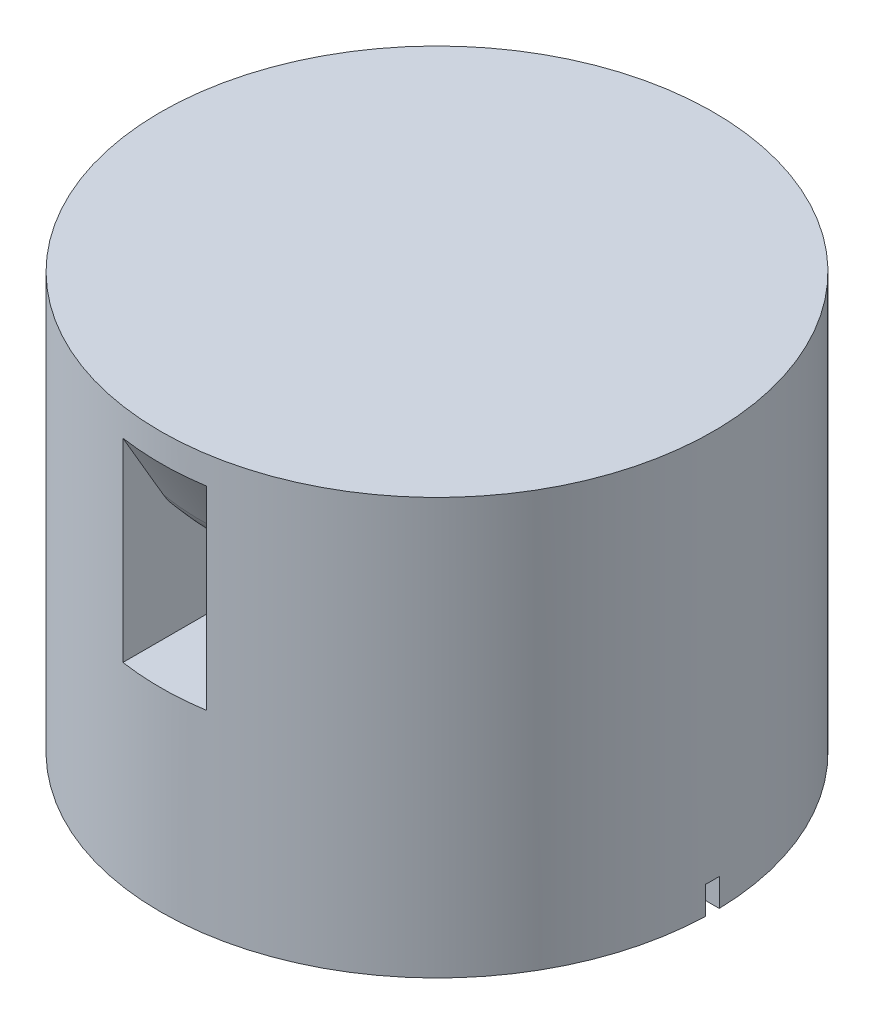
SolidWorks part; units mm, degrees
ref_plane "Front Plane" through (0, 0, 0) normal (0, 0, 1) x (1, 0, 0)
ref_plane "Top Plane" through (0, 0, 0) normal (0, 1, 0) x (1, 0, 0)
ref_plane "Right Plane" through (0, 0, 0) normal (1, 0, 0) x (0, 0, -1)
sketch "Sketch4" plane through (0, 0, 0) normal (0, 1, 0) x (1, 0, 0)
  circle A0 centre (-20.5796, -33.8554) radius 12.6543
extrude "Boss-Extrude3" add sketch "Sketch4" along normal blind 19.05
sketch "Sketch5" plane through (0, 19.05, 0) normal (0, 1, 0) x (1, 0, 0)
  line L0 (-10.0887, -40.9316) -> (-20.5796, -33.8554)
  line L1 (-20.5796, -33.8554) -> (-20.5796, -46.5097)
  circle A1 centre (-20.5796, -33.8554) radius 12.6543 construction
  dimension "D1" = 12.6543
  dimension "D2" = 12.6543
  dimension "D3" = 56
ref_plane "Plane6" through (0, 0, 46.5097) normal (0, 0, 1) x (1, 0, 0)
sketch "Sketch6" plane through (0, 0, 46.5097) normal (0, 0, 1) x (1, 0, 0)
  line L1 (-22.4389, 12.7) -> (-18.6289, 12.7)
  line L2 (-22.4389, 12.7) -> (-22.4389, 8.89)
  line L3 (-22.4389, 8.89) -> (-18.6289, 8.89)
  line L4 (-18.6289, 12.7) -> (-18.6289, 8.89)
  line L7 (-7.9253, 19.05) -> (-33.2339, 19.05) construction
  dimension "D1" = 3.81
  dimension "D4" = 6.35
sketch "Sketch8" plane through (0, 19.05, 0) normal (0, 1, 0) x (1, 0, 0)
  line L0 (-20.5796, -33.8554) -> (-33.2339, -33.8554)
  line L1 (-33.2339, -33.8554) -> (-7.9253, -33.8554)
  circle A0 centre (-20.5796, -33.8554) radius 12.6543 construction
extrude "Cut-Extrude5" cut sketch "Sketch6" against normal blind 5.08 contours L1 L4 L3 L2
chamfer "Chamfer4" distance 5.08 angle 30 1 edges at (-20.5334, 12.7, 46.5096) first distance on face at (-20.5796, 0, 46.5097)
fillet "Fillet1" radius 3.81 1 edges at (-20.533, 12.7, 43.5766)
pattern_circular "CirPattern1" count 2 over 360 about axis through (-20.5796, 19.05, 33.8554) along (0, -1, 0) of "Cut-Extrude5"
chamfer "Chamfer5" distance 5.08 angle 30 1 edges at (-20.6258, 12.7, 21.2011) first distance on face at (-20.5337, 13.335, 46.4375)
fillet "Fillet2" radius 3.81 1 edges at (-20.6262, 12.7, 24.1341)
sketch "Sketch10" plane through (0, 0, 0) normal (0, -1, 0) x (-1, 0, 0)
  line L1 (33.6612, -34.2213) -> (7.0309, -34.2213)
  line L2 (33.6612, -34.2213) -> (33.6612, -33.5863)
  line L3 (33.6612, -33.5863) -> (7.0309, -33.5863)
  line L4 (7.0309, -34.2213) -> (7.0309, -33.5863)
  line L5 (20.3461, -33.5863) -> (20.3461, -34.2213) construction
  line L6 (33.6612, -33.9038) -> (7.0309, -33.9038) construction
  dimension "D1" = 0.635
extrude "Cut-Extrude6" cut sketch "Sketch10" against normal blind 1.27
